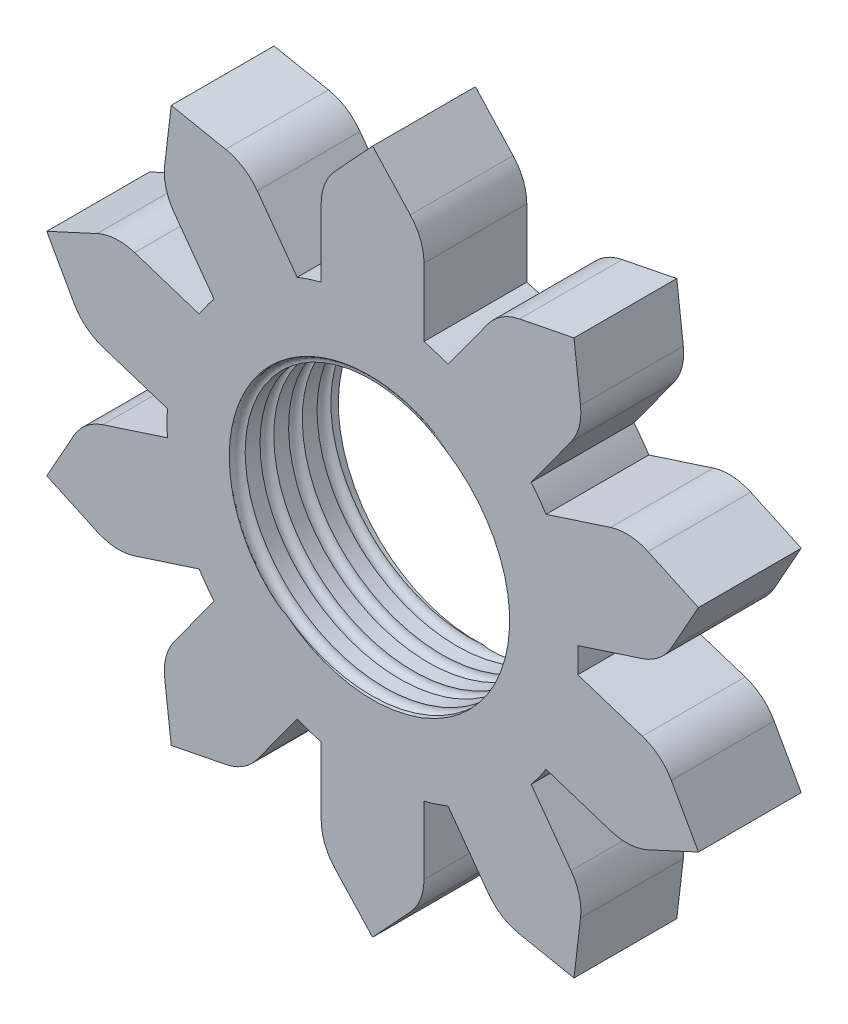
SolidWorks part; units mm, degrees
ref_plane "Front Plane" through (0, 0, 0) normal (0, 0, 1) x (1, 0, 0)
ref_plane "Top Plane" through (0, 0, 0) normal (0, 1, 0) x (1, 0, 0)
ref_plane "Right Plane" through (0, 0, 0) normal (1, 0, 0) x (0, 0, -1)
sketch "Sketch1" plane through (0, 0, 0) normal (0, 0, 1) x (1, 0, 0)
  line L0 (0, 10) -> (-1.1012, 8.8095)
  line L1 (-1.5, 7.7909) -> (-1.5, 5.8095)
  line L2 (0, 10) -> (0, 6) construction
  line L3 (1.5, 7.7909) -> (1.5, 5.8095)
  line L4 (0, 10) -> (1.1012, 8.8095)
  line L5 (3.3659, 7.1847) -> (2.2012, 5.5816)
  line L6 (5.8779, 8.0902) -> (4.2872, 7.7743)
  line L7 (5.8779, 8.0902) -> (6.0689, 6.4798)
  line L8 (5.7929, 5.4213) -> (4.6282, 3.8183)
  line L9 (6.9461, 3.8341) -> (5.0616, 3.2218)
  line L10 (9.5106, 3.0902) -> (8.038, 3.7696)
  line L11 (9.5106, 3.0902) -> (8.7186, 1.675)
  line L12 (7.8732, 0.9809) -> (5.9887, 0.3686)
  line L13 (7.8732, -0.9809) -> (5.9887, -0.3686)
  line L14 (9.5106, -3.0902) -> (8.7186, -1.675)
  line L15 (9.5106, -3.0902) -> (8.038, -3.7696)
  line L16 (6.9461, -3.8341) -> (5.0616, -3.2218)
  line L17 (5.7929, -5.4213) -> (4.6282, -3.8183)
  line L18 (5.8779, -8.0902) -> (6.0689, -6.4798)
  line L19 (5.8779, -8.0902) -> (4.2872, -7.7743)
  line L20 (3.3659, -7.1847) -> (2.2012, -5.5816)
  line L21 (1.5, -7.7909) -> (1.5, -5.8095)
  line L22 (0, -10) -> (1.1012, -8.8095)
  line L23 (0, -10) -> (-1.1012, -8.8095)
  line L24 (-1.5, -7.7909) -> (-1.5, -5.8095)
  line L25 (-3.3659, -7.1847) -> (-2.2012, -5.5816)
  line L26 (-5.8779, -8.0902) -> (-4.2872, -7.7743)
  line L27 (-5.8779, -8.0902) -> (-6.0689, -6.4798)
  line L28 (-5.7929, -5.4213) -> (-4.6282, -3.8183)
  line L29 (-6.9461, -3.8341) -> (-5.0616, -3.2218)
  line L30 (-9.5106, -3.0902) -> (-8.038, -3.7696)
  line L31 (-9.5106, -3.0902) -> (-8.7186, -1.675)
  line L32 (-7.8732, -0.9809) -> (-5.9887, -0.3686)
  line L33 (-7.8732, 0.9809) -> (-5.9887, 0.3686)
  line L34 (-9.5106, 3.0902) -> (-8.7186, 1.675)
  line L35 (-9.5106, 3.0902) -> (-8.038, 3.7696)
  line L36 (-6.9461, 3.8341) -> (-5.0616, 3.2218)
  line L37 (-5.7929, 5.4213) -> (-4.6282, 3.8183)
  line L38 (-5.8779, 8.0902) -> (-6.0689, 6.4798)
  line L39 (-5.8779, 8.0902) -> (-4.2872, 7.7743)
  line L40 (-3.3659, 7.1847) -> (-2.2012, 5.5816)
  circle A0 centre (0, 0) radius 4
  circle A1 centre (0, 0) radius 6
  arc A2 (1.5, 7.7909) -> (1.1012, 8.8095) centre (0, 7.7909) ccw
  arc A3 (-1.5, 7.7909) -> (-1.1012, 8.8095) centre (0, 7.7909) cw
  arc A4 (3.3659, 7.1847) -> (4.2872, 7.7743) centre (4.5794, 6.303) cw
  arc A5 (5.7929, 5.4213) -> (6.0689, 6.4798) centre (4.5794, 6.303) ccw
  arc A6 (6.9461, 3.8341) -> (8.038, 3.7696) centre (7.4096, 2.4075) cw
  arc A7 (7.8732, 0.9809) -> (8.7186, 1.675) centre (7.4096, 2.4075) ccw
  arc A8 (7.8732, -0.9809) -> (8.7186, -1.675) centre (7.4096, -2.4075) cw
  arc A9 (6.9461, -3.8341) -> (8.038, -3.7696) centre (7.4096, -2.4075) ccw
  arc A10 (5.7929, -5.4213) -> (6.0689, -6.4798) centre (4.5794, -6.303) cw
  arc A11 (3.3659, -7.1847) -> (4.2872, -7.7743) centre (4.5794, -6.303) ccw
  arc A12 (1.5, -7.7909) -> (1.1012, -8.8095) centre (0, -7.7909) cw
  arc A13 (-1.5, -7.7909) -> (-1.1012, -8.8095) centre (0, -7.7909) ccw
  arc A14 (-3.3659, -7.1847) -> (-4.2872, -7.7743) centre (-4.5794, -6.303) cw
  arc A15 (-5.7929, -5.4213) -> (-6.0689, -6.4798) centre (-4.5794, -6.303) ccw
  arc A16 (-6.9461, -3.8341) -> (-8.038, -3.7696) centre (-7.4096, -2.4075) cw
  arc A17 (-7.8732, -0.9809) -> (-8.7186, -1.675) centre (-7.4096, -2.4075) ccw
  arc A18 (-7.8732, 0.9809) -> (-8.7186, 1.675) centre (-7.4096, 2.4075) cw
  arc A19 (-6.9461, 3.8341) -> (-8.038, 3.7696) centre (-7.4096, 2.4075) ccw
  arc A20 (-5.7929, 5.4213) -> (-6.0689, 6.4798) centre (-4.5794, 6.303) cw
  arc A21 (-3.3659, 7.1847) -> (-4.2872, 7.7743) centre (-4.5794, 6.303) ccw
  point P88 (0, 0)
  dimension "D1" = 12
  dimension "D2" = 8
  dimension "D6" = 10
  dimension "D3" = 4
  dimension "D4" = 1.5
  dimension "D5" = 3
extrude "Boss-Extrude1" add sketch "Sketch1" along normal blind 3
sketch "Sketch2" plane through (0, 0, 0) normal (0, 0, 1) x (1, 0, 0)
  circle A0 centre (0, 0) radius 4
  dimension "D1" = 8
curve "Helix/Spiral1" pitch 0.8333 height 3.9583 turns 4.75
sketch "Sketch4" plane through (0, 0, 0) normal (1, 0, 0) x (0, 0, -1)
  circle A0 centre (-0.2083, -4) radius 0.2
  dimension "D1" = 0.4
sweep "Cut-Sweep8" cut profiles "Sketch4" path "Helix/Spiral1"
sketch "Sketch6" plane through (0, 0, 0) normal (0, 0, 1) x (1, 0, 0)
  circle A0 centre (0, 0) radius 6
